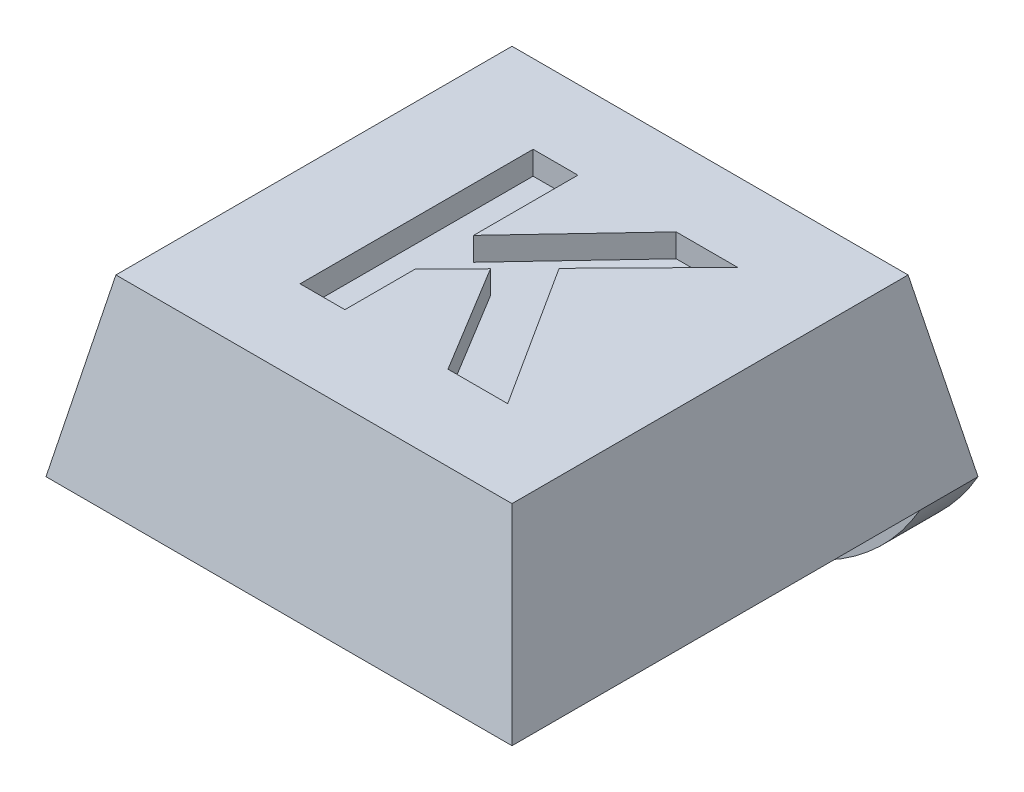
SolidWorks part; units mm, degrees
ref_plane "Front Plane" through (0, 0, 0) normal (0, 0, 1) x (1, 0, 0)
ref_plane "Top Plane" through (0, 0, 0) normal (0, 1, 0) x (1, 0, 0)
ref_plane "Right Plane" through (0, 0, 0) normal (1, 0, 0) x (0, 0, -1)
sketch "Sketch1" plane through (0, 0, 0) normal (0, 1, 0) x (1, 0, 0)
  line L1 (0, 0) -> (8, 0)
  line L2 (0, 0) -> (0, 8)
  line L3 (0, 8) -> (8, 8)
  line L4 (8, 0) -> (8, 8)
  dimension "D1" = 8
  dimension "D2" = 8
extrude "Boss-Extrude1" add sketch "Sketch1" along normal blind 3
sketch "Sketch2" plane through (0, 0, 0) normal (0, 0, 1) x (1, 0, 0)
  line L0 (0, 0) -> (0.6, 3)
  line L1 (0, 3) -> (8, 3) construction
  line L2 (0.6, 3) -> (0, 3)
  line L3 (0, 3) -> (0, 0)
  line L4 (8, 0) -> (7.4, 3)
  line L5 (7.4, 3) -> (8, 3)
  line L6 (8, 3) -> (8, 0)
  dimension "D1" = 0.6
  dimension "D2" = 0.6
extrude "Cut-Extrude1" cut sketch "Sketch2" against normal through all both and the other way through all
sketch "Sketch3" plane through (0, 0, 0) normal (1, 0, 0) x (0, 0, -1)
  line L0 (0, 0) -> (0.6, 3)
  line L1 (8, 3) -> (0, 3) construction
  line L2 (0.6, 3) -> (0, 3)
  line L3 (0, 3) -> (0, 0)
  line L4 (8, 3) -> (7.4, 3)
  line L5 (7.4, 3) -> (8, 0)
  line L6 (8, 3) -> (8, 0)
  dimension "D1" = 0.6
  dimension "D2" = 0.6
extrude "Cut-Extrude2" cut sketch "Sketch3" along normal blind 11
sketch "Sketch4" plane through (0, 0, 0) normal (0, -1, 0) x (1, 0, 0)
  line L0 (8, 0) -> (8, -8) construction
  line L3 (0, 0) -> (8, 0) construction
  circle A0 centre (4, -3.75) radius 1.8
  dimension "D1" = 3.6
  dimension "D2" = 4
  dimension "D3" = 3.75
extrude "Cut-Extrude3" cut sketch "Sketch4" against normal blind 0.8
sketch "Sketch5" plane through (0, 0, 0) normal (0, -1, 0) x (1, 0, 0)
  line L0 (8, 0) -> (8, -8) construction
  line L1 (0, -8) -> (8, -8)
  line L2 (0, -8) -> (0, -7)
  line L3 (0, -7) -> (8, -7)
  line L4 (8, -8) -> (8, -7)
  dimension "D1" = 1
extrude "Boss-Extrude2" add sketch "Sketch5" along normal blind 2
fillet "Fillet1" radius 4 2 edges at (8, -2, -7.5) (0, -2, -7.5)
sketch "Sketch6" plane through (0, 3, 0) normal (0, 1, 0) x (1, 0, 0)
  text T0 "K" font "Arial" height 4
extrude "Cut-Extrude4" cut sketch "Sketch6" against normal blind 0.4
